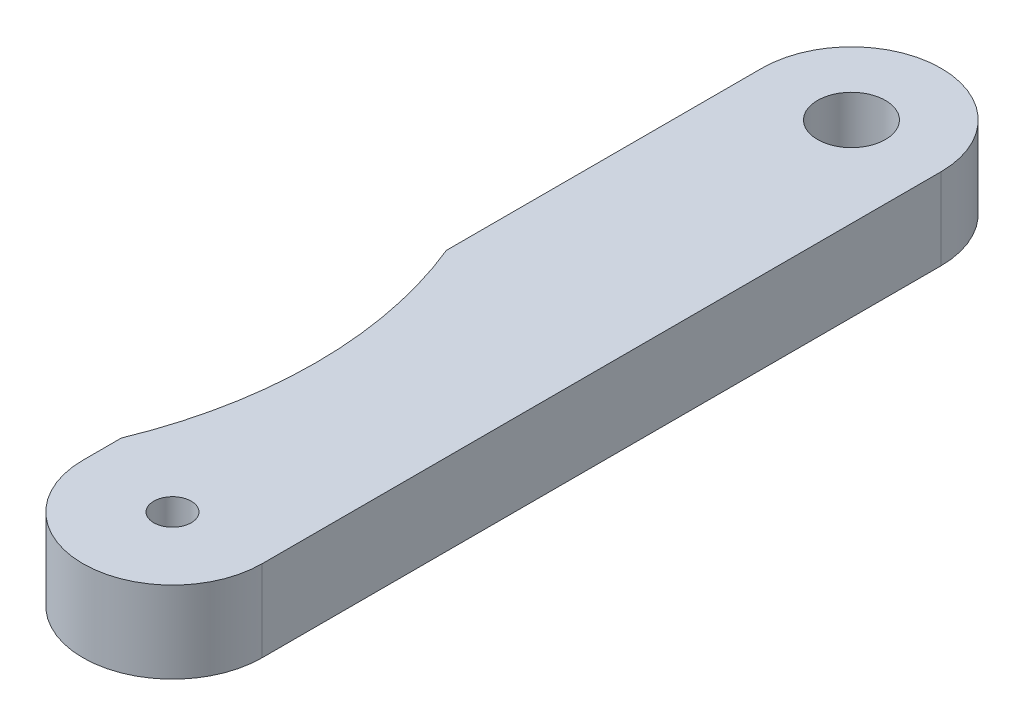
SolidWorks part; units mm, degrees
material "7075-T6, Plate (SS)"
ref_plane "Front Plane" through (0, 0, 0) normal (0, 0, 1) x (1, 0, 0)
ref_plane "Top Plane" through (0, 0, 0) normal (0, 1, 0) x (1, 0, 0)
ref_plane "Right Plane" through (0, 0, 0) normal (1, 0, 0) x (0, 0, -1)
sketch "Sketch1" plane through (0, 0, 0) normal (0, 1, 0) x (1, 0, 0)
  line L0 (0.3077, 6.5172) -> (0.3077, -25.2328)
  line L1 (8.6897, 6.5172) -> (8.6897, -25.2328)
  arc A0 (0.3077, 6.5172) -> (8.6897, 6.5172) centre (4.4987, 6.5172) cw
  arc A1 (8.6897, -25.2328) -> (0.3077, -25.2328) centre (4.4987, -25.2328) cw
  dimension "D1" = 31.75
  dimension "D2" = 8.382
extrude "Boss-Extrude1" add sketch "Sketch1" along normal blind 3.81
hole_wizard "#4-40 Tapped Hole1" positions "Sketch2" profile "Sketch3" tap size "#4-40" standard "ANSI Inch" end condition through all
sketch "Sketch2" plane through (0, 3.81, 0) normal (0, 1, 0) x (1, 0, 0)
  arc A0 (0.3077, -25.2328) -> (8.6897, -25.2328) centre (4.4987, -25.2328) ccw construction
  arc A1 (8.6897, 6.5172) -> (0.3077, 6.5172) centre (4.4987, 6.5172) ccw construction
  point P0 (4.4987, 6.5172)
  point P2 (4.4987, -25.2328)
sketch "Sketch3" plane through (4.4987, 3.81, -6.5172) normal (1, 0, 0) x (0, 0, 1)
  line L0 (0, 0) -> (0, 3.81)
  line L1 (0, 3.81) -> (0.8763, 3.81)
  line L2 (0.8763, 3.81) -> (0.8763, 0)
  line L5 (0.8763, 0) -> (0, 0)
  line L11 (0, -6.35) -> (0, 107.95) construction
  dimension "Thru Tap Drill Dia." = 1.7526
  dimension "Thru Tap Drill Depth" = 3.81
cosmetic thread "Hole Thread1" parameters "D2"=2.8448
cosmetic thread "Hole Thread2" parameters "D2"=2.8448
sketch "Sketch4" plane through (0, 3.81, 0) normal (0, 1, 0) x (1, 0, 0)
  line L0 (0.3077, -15.8348) -> (-18.1923, -15.8348) construction
  line L1 (0.3077, 6.5172) -> (0.3077, -25.2328) construction
  line L2 (0.3077, -23.4341) -> (0.3077, -8.2354)
  arc A0 (0.3077, -23.4341) -> (0.3077, -8.2354) centre (-18.1923, -15.8348) ccw
  circle A1 centre (4.4987, -25.2328) radius 0.8763 construction
  dimension "D1" = 20
  dimension "D2" = 9.398
  dimension "D3" = 18.5
extrude "Cut-Extrude1" cut sketch "Sketch4" against normal through all
sketch "Sketch5" plane through (0, 3.81, 0) normal (0, 1, 0) x (1, 0, 0)
  circle A0 centre (4.4987, 6.5172) radius 1.5875
extrude "Cut-Extrude2" cut sketch "Sketch5" against normal through all
